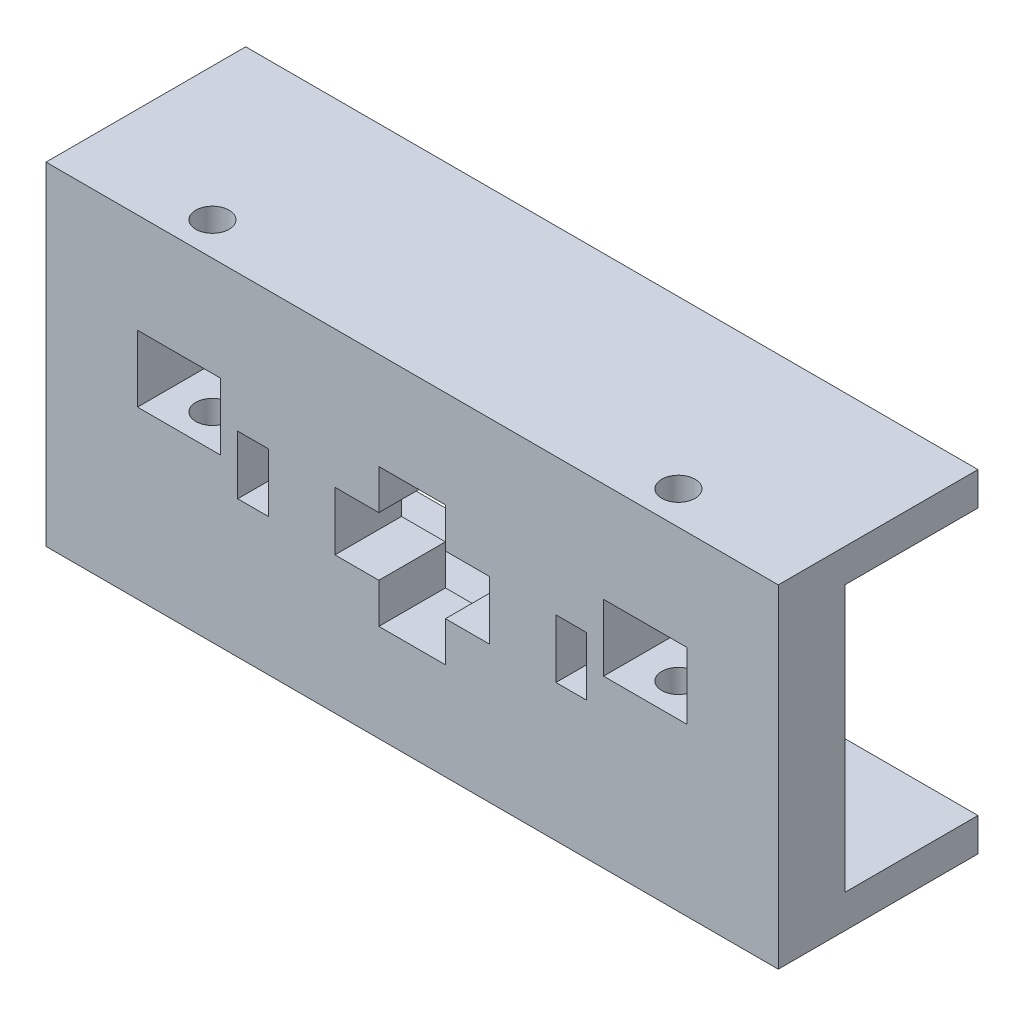
SolidWorks part; units mm, degrees
ref_plane "Front Plane" through (0, 0, 0) normal (0, 0, 1) x (1, 0, 0)
ref_plane "Top Plane" through (0, 0, 0) normal (0, 1, 0) x (1, 0, 0)
ref_plane "Right Plane" through (0, 0, 0) normal (1, 0, 0) x (0, 0, -1)
sketch "Sketch1" plane through (0, 0, 0) normal (0, 0, 1) x (1, 0, 0)
  line L1 (0, -6.604) -> (-3.175, -6.604)
  line L2 (-3.175, -12.7) -> (-3.175, -13.6525)
  line L3 (-3.175, -13.6525) -> (0, -13.6525)
  line L4 (3.175, -13.6525) -> (3.175, -12.7)
  line L5 (3.175, -6.604) -> (0, -6.604)
  line L7 (0, -13.6525) -> (3.175, -13.6525)
  line L8 (3.175, 2.794) -> (7.366, 2.794)
  line L9 (16.637, 2.794) -> (16.637, -2.794)
  line L10 (16.637, -2.794) -> (13.716, -2.794)
  line L11 (3.175, -2.794) -> (3.175, -6.604)
  line L12 (3.175, -12.7) -> (34.925, -12.7)
  line L13 (34.925, -12.7) -> (34.925, 12.7)
  line L14 (34.925, 12.7) -> (3.175, 12.7)
  line L15 (3.175, 6.604) -> (3.175, 2.794)
  line L17 (0, 6.604) -> (3.175, 6.604)
  line L18 (3.175, 12.7) -> (3.175, 13.6525)
  line L19 (3.175, 13.6525) -> (0, 13.6525)
  line L20 (-3.175, 13.6525) -> (-3.175, 12.7)
  line L21 (-3.175, 6.604) -> (0, 6.604)
  line L23 (0, 13.6525) -> (-3.175, 13.6525)
  line L24 (-3.175, -2.794) -> (-7.366, -2.794)
  line L25 (-16.637, -2.794) -> (-16.637, 2.794)
  line L26 (-16.637, 2.794) -> (-13.716, 2.794)
  line L27 (-3.175, 2.794) -> (-3.175, 6.604)
  line L28 (-3.175, 12.7) -> (-34.925, 12.7)
  line L29 (-34.925, 12.7) -> (-34.925, -12.7)
  line L30 (-34.925, -12.7) -> (-3.175, -12.7)
  line L31 (-3.175, -6.604) -> (-3.175, -2.794)
  line L32 (-13.716, 2.794) -> (-13.716, -2.794)
  line L33 (-7.366, -2.794) -> (-7.366, 2.794)
  line L34 (13.716, -2.794) -> (13.716, 2.794)
  line L35 (7.366, 2.794) -> (7.366, -2.794)
  line L36 (-13.716, -2.794) -> (-16.637, -2.794)
  line L37 (-7.366, 2.794) -> (-3.175, 2.794)
  line L38 (7.366, -2.794) -> (3.175, -2.794)
  line L39 (13.716, 2.794) -> (16.637, 2.794)
  line L41 (-34.925, 12.7) -> (34.925, 12.7)
  line L42 (-34.925, 12.7) -> (-34.925, 15.875)
  line L43 (-34.925, 15.875) -> (34.925, 15.875)
  line L44 (34.925, 12.7) -> (34.925, 15.875)
  line L45 (34.925, -12.7) -> (-34.925, -12.7)
  line L46 (34.925, -12.7) -> (34.925, -15.875)
  line L47 (34.925, -15.875) -> (-34.925, -15.875)
  line L48 (-34.925, -12.7) -> (-34.925, -15.875)
  dimension "D1" = 69.85
  dimension "D2" = 3.175
  dimension "D3" = 3.175
extrude "Boss-Extrude1" add sketch "Sketch1" against normal blind 12.7 contours L14 L44 L43 L42 L28 L20 L23 L19 L18 | L30 L48 L47 L46 L12 L4 L7 L3 L2 region at (0, -14.3187, 0) region at (0, 14.3187, 0)
extrude "Boss-Extrude2" add sketch "Sketch1<3>" along normal blind 6.35 contours L45 L12 L13 L14 L41 L28 L29 L30 L32 L36 L25 L26 L35 L38 L11 L5 L1 L31 L24 L33 L37 L27 L21 L17 L15 L8 L34 L39 L9 L10 | L14 L44 L43 L42 L28 L20 L23 L19 L18 | L30 L48 L47 L46 L12 L4 L7 L3 L2 | L20 L41 L18 L19 L23 | L4 L45 L2 L3 L7 region at (0, -13.1763, 0) region at (0, -14.3187, 0) region at (-19.05, -11.9568, 0) region at (0, 14.3187, 0) region at (0, 13.1762, 0)
sketch "Sketch1<3>" plane through (0, 0, 0) normal (0, 0, 1) x (1, 0, 0) same geometry as "Sketch1"
sketch "Sketch3" plane through (0, 15.875, 0) normal (0, 1, 0) x (1, 0, 0)
  line L0 (-22.225, -3.175) -> (22.225, -3.175) construction
  line L1 (-34.925, -6.35) -> (34.925, -6.35) construction
  circle A0 centre (22.225, -3.175) radius 1.5875
  circle A1 centre (-22.225, -3.175) radius 1.5875
  point P0 (21.4544, -3.4594)
  point P6 (0, -3.175)
  dimension "D1" = 3.175
  dimension "D2" = 44.45
  dimension "D3" = 3.175
extrude "Cut-Extrude1" cut sketch "Sketch3" against normal blind 20.32
sketch "Sketch4" plane through (0, 0, 6.35) normal (0, 0, 1) x (1, 0, 0)
  line L0 (-22.225, 0) -> (22.225, 0) construction
  line L1 (-26.1937, 0) -> (-18.2563, 0)
  line L2 (-26.1937, 0) -> (-26.1937, 6.35)
  line L3 (-26.1937, 6.35) -> (-18.2562, 6.35)
  line L4 (-18.2563, 0) -> (-18.2562, 6.35)
  line L5 (-22.225, 0) -> (-22.225, 21.6094) construction
  line L6 (22.225, 0) -> (22.225, 21.6094) construction
  line L7 (-34.925, 15.875) -> (34.925, 15.875) construction
  line L8 (0, -10.4775) -> (0, 10.4775) construction
  line L9 (26.1937, 6.35) -> (18.2562, 6.35)
  line L10 (18.2563, 0) -> (18.2562, 6.35)
  line L11 (26.1937, 0) -> (18.2563, 0)
  line L12 (26.1937, 0) -> (26.1937, 6.35)
  point P7 (0, 0)
  point P12 (-22.225, 6.35)
  dimension "D1" = 44.45
  dimension "D2" = 15.875
  dimension "D3" = 7.9375
  dimension "D4" = 6.35
extrude "Cut-Extrude2" cut sketch "Sketch4" against normal blind 6.35
